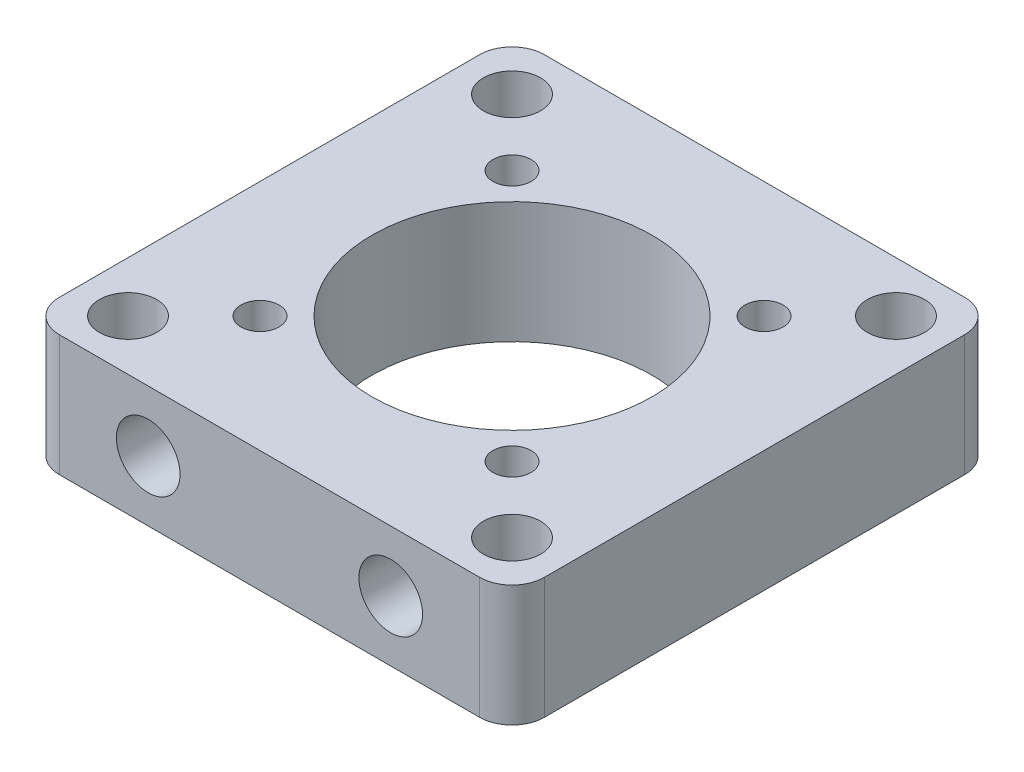
SolidWorks part; units mm, degrees
material "Alum Plate"
ref_plane "Front Plane" through (0, 0, 0) normal (0, 0, 1) x (1, 0, 0)
ref_plane "Top Plane" through (0, 0, 0) normal (0, 1, 0) x (1, 0, 0)
ref_plane "Right Plane" through (0, 0, 0) normal (1, 0, 0) x (0, 0, -1)
other "Bounding Box"
ref_plane "Default Plane" through (-8.9266, -12.7485, 0) normal (-0.1736, 0.9848, 0) x (0.9848, 0.1736, 0)
sketch "Sketch1" plane through (0, 0, 0) normal (0, 1, 0) x (1, 0, 0)
  line L0 (0, -12.5) -> (0, 12.5) construction
  line L1 (-14.5, 0) -> (0, 14.5) construction
  line L2 (-19.05, 19.05) -> (19.05, 19.05)
  line L3 (-19.05, 19.05) -> (-19.05, -19.05)
  line L4 (-19.05, -19.05) -> (19.05, -19.05)
  line L5 (19.05, 19.05) -> (19.05, -19.05)
  line L6 (-19.05, 19.05) -> (19.05, -19.05) construction
  line L7 (-19.05, -19.05) -> (19.05, 19.05) construction
  line L8 (8.8388, 8.8388) -> (-8.8388, 8.8388) construction
  line L9 (8.8388, 8.8388) -> (8.8388, -8.8388) construction
  line L10 (8.8388, -8.8388) -> (-8.8388, -8.8388) construction
  line L11 (-8.8388, 8.8388) -> (-8.8388, -8.8388) construction
  line L12 (8.8388, 8.8388) -> (-8.8388, -8.8388) construction
  line L13 (8.8388, -8.8388) -> (-8.8388, 8.8388) construction
  line L14 (-14.5, 0) -> (0, -14.5) construction
  line L15 (0, 14.5) -> (14.5, 0) construction
  line L16 (0, -14.5) -> (14.5, 0) construction
  line L17 (-14.5, 0) -> (14.5, 0) construction
  line L18 (0, 14.5) -> (0, -14.5) construction
  circle A0 centre (-15.24, 15.24) radius 1.3843 construction
  circle A1 centre (15.24, 15.24) radius 1.3843 construction
  circle A2 centre (15.24, -15.24) radius 1.3843 construction
  circle A3 centre (-15.24, -15.24) radius 1.3843 construction
  circle A4 centre (0, 0) radius 4
  circle A5 centre (8.8388, 8.8388) radius 1.5875
  circle A6 centre (8.8388, -8.8388) radius 1.5875
  circle A7 centre (-8.8388, -8.8388) radius 1.5875
  circle A8 centre (-8.8388, 8.8388) radius 1.5875
  circle A9 centre (-14.5, 0) radius 1.25
  circle A10 centre (0, 14.5) radius 1.25
  circle A11 centre (14.5, 0) radius 1.25
  circle A12 centre (0, -14.5) radius 1.25
  point P3 (0, 0)
  circle B0 centre (-9.8995, -9.8995) radius 1.2645 construction
  circle B1 centre (0, -8) radius 1.5875 construction
  circle B2 centre (0, 0) radius 4 construction
  circle B3 centre (9.8995, 9.8995) radius 1.2645 construction
  circle B4 centre (0, 8) radius 1.5875 construction
  circle B5 centre (9.8995, -9.8995) radius 1.2645 construction
  circle B6 centre (0, -12.5) radius 1.5875 construction
  circle B7 centre (-9.5, 0) radius 1.5875 construction
  circle B8 centre (-15.24, 15.24) radius 1.3843 construction
  circle B9 centre (15.24, 15.24) radius 1.3843 construction
  circle B10 centre (15.24, -15.24) radius 1.3843 construction
  circle B11 centre (-15.24, -15.24) radius 1.3843 construction
  circle B12 centre (9.5, 0) radius 1.5875 construction
  circle B13 centre (-9.8995, 9.8995) radius 1.2645 construction
  circle B14 centre (0, 12.5) radius 1.5875 construction
  dimension "D2" = 3.175
  dimension "D4" = 2.5
  dimension "D1" = 38.1
  dimension "D3" = 25
  dimension "D5" = 29
sketch_block_instance "Block-36mm gearbox motor block holes-1"
sketch_block "Block-36mm gearbox motor block holes"
extrude "Boss-Extrude1" add sketch "Sketch1" along normal mid plane 6.35 contours L5 L2 L3 L4 A12 A11 A9 A8 A10 A7 A6 A5 A4 A3 A2 A1 A0 region at (0, 0, -18.5112)
sketch "Sketch4" plane through (0, 0, 19.05) normal (0, 0, 1) x (1, 0, 0)
  line L0 (-5.5562, 0) -> (0, 0) construction
  line L1 (0, 0) -> (5.5562, 0) construction
  circle A0 centre (-5.5562, 0) radius 1.7272
  circle A1 centre (5.5562, 0) radius 1.7272
  dimension "D2" = 3.4544
  dimension "D1" = 11.1125
extrude "Cut-Extrude2" cut sketch "Sketch4" against normal blind 10.795
sketch "Sketch7" plane through (0, -3.175, 0) normal (0, -1, 0) x (1, 0, 0)
  line L0 (-19.05, 15.0813) -> (-15.0813, 15.0813) construction
  line L1 (-19.05, -19.05) -> (-19.05, 19.05) construction
  line L2 (-15.0813, 15.0813) -> (-15.0813, 19.05) construction
  line L3 (-19.05, 19.05) -> (19.05, 19.05) construction
  line L4 (0, 0) -> (-15.0813, 15.0813) construction
  line L5 (0, 0) -> (15.0813, 15.0812) construction
  circle A0 centre (-15.0813, 15.0813) radius 2.1526
  circle A1 centre (15.0813, 15.0812) radius 2.1527
  circle A2 centre (15.0812, -15.0813) radius 2.1527
  circle A3 centre (-15.0813, -15.0812) radius 2.1526
  dimension "D2" = 4.3053
  dimension "D1" = 3.9688
  dimension "D4" = 90
  dimension "D3" = 4
extrude "Cut-Extrude3" cut sketch "Sketch7" against normal through all
pattern_circular "CirPattern1" count 4 over 360 about axis through (0, 3.175, 0) along (0, -1, 0) of "Cut-Extrude2"
ref_plane "Plane1" through (0, -32.512, 0) normal (0, -1, 0) x (-1, 0, 0)
sketch "Sketch6" plane through (0, -32.512, 0) normal (0, -1, 0) x (-1, 0, 0)
  line L0 (19.05, 19.05) -> (-19.05, 19.05) construction
  line L1 (19.05, 19.05) -> (19.05, -19.05) construction
  line L2 (19.05, -19.05) -> (-19.05, -19.05) construction
  line L3 (-19.05, 19.05) -> (-19.05, -19.05) construction
  line L12 (19.05, 19.05) -> (-19.05, 19.05)
  line L13 (19.05, 19.05) -> (19.05, -19.05)
  line L14 (19.05, -19.05) -> (-19.05, -19.05)
  line L15 (-19.05, 19.05) -> (-19.05, -19.05)
  circle A8 centre (0, 0) radius 6.5
  circle A17 centre (-15.0812, 15.0813) radius 2.1526
  circle A18 centre (15.0813, 15.0812) radius 2.1526
  circle A19 centre (15.0813, -15.0813) radius 2.1527
  circle A20 centre (-15.0813, -15.0812) radius 2.1526
  circle A21 centre (-15.0812, 15.0813) radius 2.1527 construction
  dimension "D2" = 13
extrude "Boss-Extrude2" add sketch "Sketch6" along normal blind 3.175 separate body
fillet "Fillet1" radius 2.54 4 edges at (-19.05, 0, 19.05) (-19.05, 0, -19.05) (19.05, 0, -19.05) (19.05, 0, 19.05)
fillet "Fillet2" radius 2.54 4 edges at (-19.05, -34.0995, 19.05) (-19.05, -34.0995, -19.05) (19.05, -34.0995, -19.05) (19.05, -34.0995, 19.05)
sketch "Sketch8" plane through (0, -32.512, 0) normal (0, 1, 0) x (1, 0, 0)
  line L0 (-16.51, 19.05) -> (16.51, 19.05) construction
  circle A0 centre (-15.0813, 15.0812) radius 2.3876
  circle A1 centre (-15.0813, 15.0812) radius 3.9688
  dimension "D1" = 4.7752
extrude "Boss-Extrude3" add sketch "Sketch8" along normal offset from surface (4.572 mm away) 24.765 separate body up to face at (-15.0813, -3.175, -17.2339)
pattern_circular "CirPattern2" count 4 over 360 about axis through (0, -35.687, 0) along (0, 1, 0) of bodies 110
delete or keep bodies "Body-Delete/Keep 1" [suppressed] type keep bodies bodies 108
delete or keep bodies "Body-Delete/Keep 2" [suppressed] type keep bodies bodies 107
delete or keep bodies "Body-Delete/Keep 3" [suppressed] bodies 113
delete or keep bodies "Body-Delete/Keep 4" [suppressed] type delete bodies bodies 107
sketch "Sketch9" plane through (0, 3.175, 0) normal (0, 1, 0) x (1, 0, 0)
  line L0 (-16.51, -19.05) -> (16.51, -19.05) construction
  line L1 (-19.05, 19.05) -> (19.05, 19.05)
  line L2 (-19.05, 19.05) -> (-19.05, -19.05)
  line L3 (-19.05, -19.05) -> (19.05, -19.05)
  line L4 (19.05, 19.05) -> (19.05, -19.05)
  line L5 (-19.05, 19.05) -> (19.05, -19.05) construction
  line L6 (-19.05, -19.05) -> (19.05, 19.05) construction
  point P0 (0, 0)
extrude "Boss-Extrude4" add sketch "Sketch9" along normal blind 9.525 from offset 27.559 separate body
sketch "Sketch12" plane through (0, 0, -19.05) normal (0, 0, -1) x (-1, 0, 0)
  line L0 (-19.05, 35.4965) -> (-9.525, 35.4965) construction
  line L1 (-19.05, 40.259) -> (-19.05, 30.734) construction
  line L2 (-9.525, 35.4965) -> (9.525, 35.4965) construction
  line L3 (9.525, 35.4965) -> (19.05, 35.4965) construction
  line L4 (19.05, 40.259) -> (19.05, 30.734) construction
  circle A0 centre (-9.525, 35.4965) radius 2.5
  circle A1 centre (9.525, 35.4965) radius 2.5
  dimension "D2" = 5
  dimension "D1" = 19.05
extrude "Cut-Extrude5" cut sketch "Sketch12" against normal blind 9.525
mirror "Mirror1" about plane through (0, 0, 0) normal (0, 0, 1) of "Cut-Extrude5"
fillet "Fillet3" radius 2.54 4 edges at (19.05, 35.4965, -19.05) (19.05, 35.4965, 19.05) (-19.05, 35.4965, 19.05) (-19.05, 35.4965, -19.05)
sketch "Sketch10" plane through (0, 40.259, 0) normal (0, 1, 0) x (1, 0, 0)
  line L1 (-9.8995, 9.8995) -> (9.8995, 9.8995) construction
  line L2 (-9.8995, 9.8995) -> (-9.8995, -9.8995) construction
  line L3 (-9.8995, -9.8995) -> (9.8995, -9.8995) construction
  line L4 (9.8995, 9.8995) -> (9.8995, -9.8995) construction
  line L5 (-9.8995, 9.8995) -> (9.8995, -9.8995) construction
  line L6 (-9.8995, -9.8995) -> (9.8995, 9.8995) construction
  line L7 (-15.0813, 15.0812) -> (15.0813, 15.0812) construction
  line L8 (-15.0813, 15.0812) -> (-15.0813, -15.0813) construction
  line L9 (-15.0813, -15.0813) -> (15.0813, -15.0813) construction
  line L10 (15.0813, 15.0812) -> (15.0813, -15.0813) construction
  line L11 (-15.0813, 15.0812) -> (15.0813, -15.0813) construction
  line L12 (-15.0813, -15.0813) -> (15.0813, 15.0812) construction
  circle A0 centre (0, 0) radius 11
  circle A1 centre (-9.8995, 9.8995) radius 1.5
  circle A2 centre (9.8995, 9.8995) radius 1.5
  circle A3 centre (9.8995, -9.8995) radius 1.5
  circle A4 centre (-9.8995, -9.8995) radius 1.5
  circle A5 centre (-15.0813, -15.0813) radius 2.2479
  circle A6 centre (-15.0813, 15.0812) radius 2.2479
  circle A7 centre (15.0813, 15.0812) radius 2.2479
  circle A8 centre (15.0813, -15.0813) radius 2.2479
  dimension "D2" = 22
  dimension "D4" = 4.4958
  dimension "D5" = 3
  dimension "D1" = 28
  dimension "D3" = 30.1625
extrude "Cut-Extrude4" cut sketch "Sketch10" against normal through all
delete or keep bodies "Body-Delete/Keep 5" type keep bodies bodies 115
